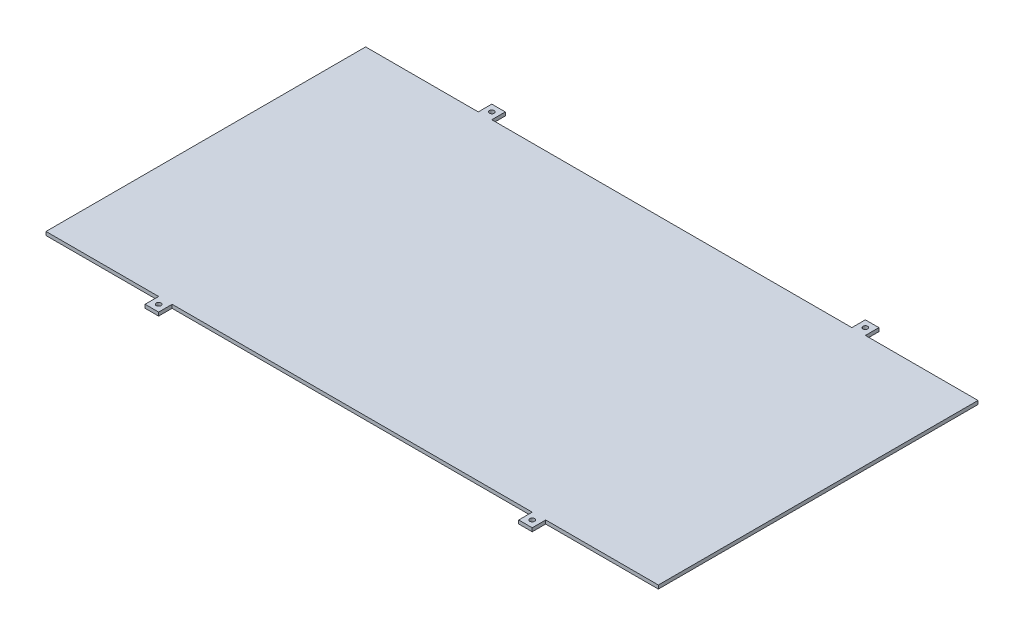
SolidWorks part; units mm, degrees
material "5052-H34"
ref_plane "Front Plane" through (0, 0, 0) normal (0, 0, 1) x (1, 0, 0)
ref_plane "Top Plane" through (0, 0, 0) normal (0, 1, 0) x (1, 0, 0)
ref_plane "Right Plane" through (0, 0, 0) normal (1, 0, 0) x (0, 0, -1)
sketch "Sketch1" plane through (0, 0, 0) normal (0, 0, 1) x (1, 0, 0)
  line L0 (-580.595, 2.8542) -> (-36.865, 2.8542)
  line L1 (-36.865, 2.8542) -> (-36.865, -0.3208)
  line L3 (-36.865, -0.3208) -> (-580.595, -0.3208)
  line L6 (-580.595, 2.8542) -> (-580.595, -0.3208)
  point P2 (-580.595, 2.8542)
  dimension "D1" = 3.175
  dimension "D2" = 543.73
  dimension "D3" = 36.865
  dimension "D4" = 2.8542
extrude "Boss-Extrude1" add sketch "Sketch1" along normal blind 283.825
sketch "GasketGroove" plane through (0, -0.3208, 0) normal (0, -1, 0) x (1, 0, 0)
  line L0 (-577.595, 279.825) -> (-577.595, 4)
  line L1 (-576.595, 3) -> (-40.865, 3)
  line L2 (-39.865, 4) -> (-39.865, 279.825)
  line L3 (-40.865, 280.825) -> (-576.595, 280.825)
  line L4 (-579.595, 282.825) -> (-579.595, 1) construction
  line L5 (-577.595, 282.825) -> (-577.595, 1) construction
  line L6 (-37.865, 280.825) -> (-579.595, 280.825) construction
  line L7 (-579.595, 3) -> (-37.865, 3) construction
  line L8 (-39.865, 1) -> (-39.865, 282.825) construction
  line L9 (-579.595, 1) -> (-37.865, 1) construction
  line L10 (-37.865, 282.825) -> (-579.595, 282.825) construction
  line L11 (-37.865, 1) -> (-37.865, 282.825) construction
  line L14 (-37.865, 1) -> (-37.865, 282.825)
  line L15 (-579.595, 1) -> (-37.865, 1)
  line L16 (-579.595, 282.825) -> (-579.595, 1)
  line L17 (-37.865, 282.825) -> (-579.595, 282.825)
  line L18 (-37.865, 2) -> (-37.865, 281.825)
  line L19 (-578.595, 1) -> (-38.865, 1)
  line L20 (-579.595, 281.825) -> (-579.595, 2)
  line L21 (-38.865, 282.825) -> (-578.595, 282.825)
  arc A0 (-579.595, 2) -> (-578.595, 1) centre (-578.595, 2) ccw
  arc A1 (-579.595, 281.825) -> (-578.595, 282.825) centre (-578.595, 281.825) cw
  arc A2 (-37.865, 281.825) -> (-38.865, 282.825) centre (-38.865, 281.825) ccw
  arc A3 (-38.865, 1) -> (-37.865, 2) centre (-38.865, 2) ccw
  arc A4 (-40.865, 3) -> (-39.865, 4) centre (-40.865, 4) ccw
  arc A5 (-576.595, 3) -> (-577.595, 4) centre (-576.595, 4) cw
  arc A6 (-576.595, 280.825) -> (-577.595, 279.825) centre (-576.595, 279.825) ccw
  arc A7 (-39.865, 279.825) -> (-40.865, 280.825) centre (-40.865, 279.825) ccw
  dimension "D6" = 1
  dimension "D7" = 1
  dimension "D8" = 1
  dimension "D9" = 1
  dimension "D10" = 1
  dimension "D11" = 1
  dimension "D12" = 1
  dimension "D13" = 1
  dimension "D1" = 1
  dimension "D2" = 2
  dimension "D3" = 2
  dimension "D4" = 2
  dimension "D5" = 2
extrude "Cut-Extrude1" cut sketch "GasketGroove" against normal blind 1.3
sketch "Sketch2" plane through (0, 2.8542, 0) normal (0, 1, 0) x (1, 0, 0)
  line L4 (-580.595, -283.825) -> (-580.595, 0) construction
  line L5 (-480.595, -283.825) -> (-468.595, -283.825)
  line L6 (-480.595, -283.825) -> (-480.595, -295.825)
  line L7 (-480.595, -295.825) -> (-468.595, -295.825)
  line L8 (-468.595, -283.825) -> (-468.595, -295.825)
  line L9 (-148.865, -283.825) -> (-136.865, -283.825)
  line L10 (-148.865, -283.825) -> (-148.865, -295.825)
  line L11 (-148.865, -295.825) -> (-136.865, -295.825)
  line L12 (-136.865, -283.825) -> (-136.865, -295.825)
  line L17 (-136.865, 0) -> (-148.865, 0)
  line L18 (-136.865, 0) -> (-136.865, 12)
  line L19 (-136.865, 12) -> (-148.865, 12)
  line L20 (-148.865, 0) -> (-148.865, 12)
  line L21 (-36.865, -283.825) -> (-36.865, 0) construction
  line L22 (-480.595, -289.825) -> (-468.595, -289.825) construction
  line L23 (-480.595, 0) -> (-468.595, 0)
  line L24 (-480.595, 0) -> (-480.595, 12)
  line L25 (-480.595, 12) -> (-468.595, 12)
  line L26 (-468.595, 0) -> (-468.595, 12)
  line L27 (-142.865, -295.825) -> (-142.865, -283.825) construction
  line L28 (-148.865, 6) -> (-136.865, 6) construction
  line L29 (-480.595, 6) -> (-468.595, 6) construction
  circle A0 centre (-474.595, -289.825) radius 2.1
  circle A1 centre (-142.865, -289.825) radius 2.1
  circle A2 centre (-142.865, 6) radius 2.1
  circle A3 centre (-474.595, 6) radius 2.1
  dimension "D10" = 4.2
  dimension "D11" = 4.2
  dimension "D12" = 4.2
  dimension "D13" = 4.2
  dimension "D1" = 12
  dimension "D2" = 12
  dimension "D3" = 12
  dimension "D4" = 100
  dimension "D5" = 100
  dimension "D6" = 100
  dimension "D7" = 12
  dimension "D8" = 100
  dimension "D9" = 12
extrude "Boss-Extrude2" add sketch "Sketch2" against normal blind 3.125
